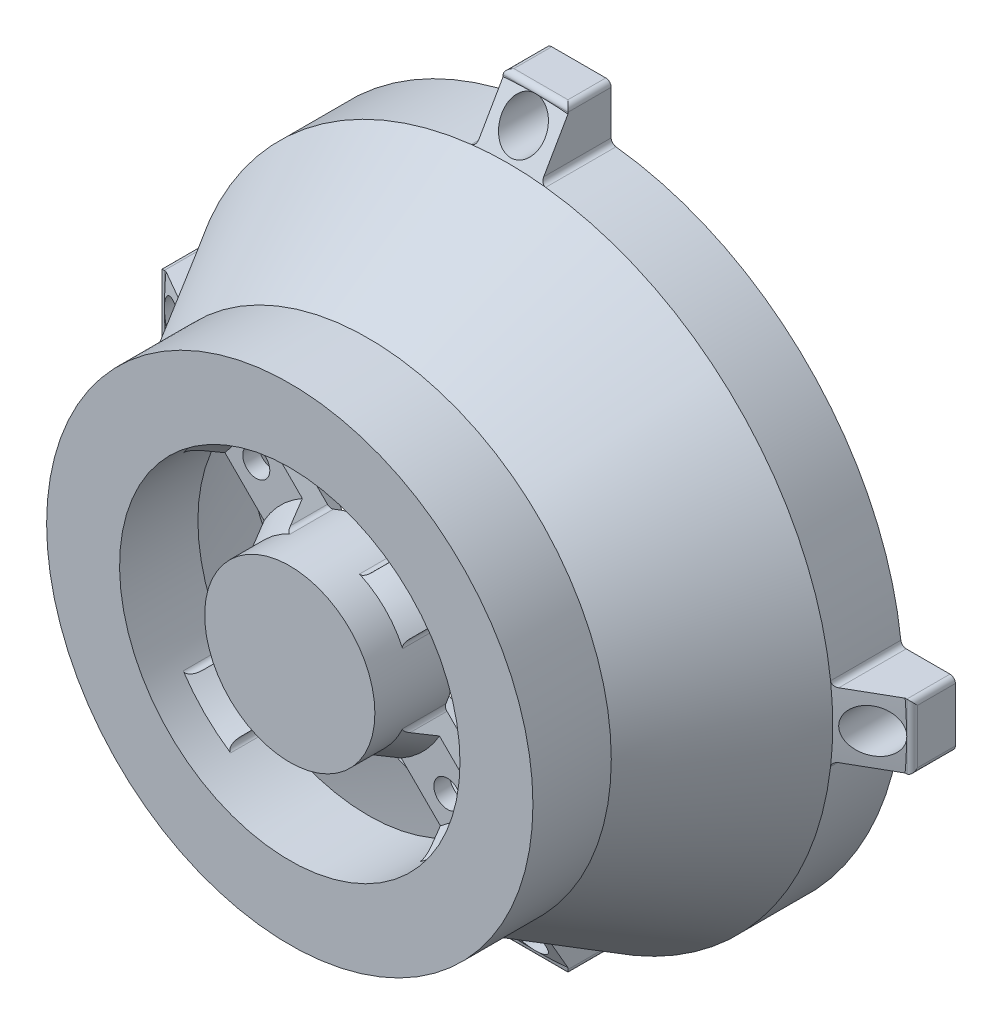
SolidWorks part; units mm, degrees
note: The reader was unsure of these and kept them because the rebuilt part matched: shared geometry of "Sketch1<3>".
ref_plane "Front Plane" through (0, 0, 0) normal (0, 0, 1) x (1, 0, 0)
ref_plane "Top Plane" through (0, 0, 0) normal (0, 1, 0) x (1, 0, 0)
ref_plane "Right Plane" through (0, 0, 0) normal (1, 0, 0) x (0, 0, -1)
sketch "Sketch1" plane through (0, 0, 0) normal (0, 0, 1) x (1, 0, 0)
  line L0 (0, 45) -> (0, 0) construction
  line L1 (17.6777, 17.6777) -> (0, 0) construction
  circle A0 centre (0, 0) radius 45
  circle A1 centre (0, 0) radius 25 construction
  circle A2 centre (17.6777, 17.6777) radius 2.5
  circle A3 centre (17.6777, -17.6777) radius 2.5
  circle A4 centre (-17.6777, -17.6777) radius 2.5
  circle A5 centre (-17.6777, 17.6777) radius 2.5
  circle A6 centre (0, 0) radius 15.75
  circle A7 centre (0, 0) radius 31.5
  point P16 (0, 0)
  point P27 (-1.0882, 1.0882)
  point P29 (2.5, -2.5)
  point P30 (0, 0)
  dimension "D2" = 50
  dimension "D4" = 5
  dimension "D6" = 31.5
  dimension "D7" = 63
  dimension "D8" = 90
  dimension "D3" = 45
  dimension "D5" = 4
extrude "Boss-Extrude1" add sketch "Sketch1" along normal blind 14.5 contours A6 | A0 A7
extrude "Boss-Extrude2" add sketch "Sketch1<3>" along normal blind 8 contours A7 A2 A3 A4 A5 A6
sketch "Sketch1<3>" plane through (0, 0, 0) normal (0, 0, 1) x (1, 0, 0) same geometry as "Sketch1"
sketch "Sketch6" plane through (0, 0, 8) normal (0, 0, 1) x (1, 0, 0)
  line L0 (-17.6777, 17.6777) -> (-22.2739, 22.2739) construction
  line L1 (-18.4559, 25.527) -> (-7.0253, 14.0964)
  line L2 (-21.2132, 14.1421) -> (-14.1421, 21.2132) construction
  line L3 (-14.0964, 7.0253) -> (-25.527, 18.4559)
  line L4 (25.527, 18.4559) -> (14.0964, 7.0253)
  line L5 (7.0253, 14.0964) -> (18.4559, 25.527)
  line L6 (18.4559, -25.527) -> (7.0253, -14.0964)
  line L7 (14.0964, -7.0253) -> (25.527, -18.4559)
  line L8 (-25.527, -18.4559) -> (-14.0964, -7.0253)
  line L9 (-7.0253, -14.0964) -> (-18.4559, -25.527)
  arc A0 (-25.527, 18.4559) -> (-25.527, -18.4559) centre (0, 0) ccw
  circle A1 centre (0, 0) radius 31.5 construction
  circle A2 centre (0, 0) radius 15.75 construction
  arc A3 (-14.0964, 7.0253) -> (-14.0964, -7.0253) centre (0, 0) ccw
  arc A4 (7.0253, 14.0964) -> (-7.0253, 14.0964) centre (0, 0) ccw
  arc A5 (14.0964, -7.0253) -> (14.0964, 7.0253) centre (0, 0) ccw
  arc A6 (-7.0253, -14.0964) -> (7.0253, -14.0964) centre (0, 0) ccw
  arc A7 (18.4559, 25.527) -> (-18.4559, 25.527) centre (0, 0) ccw
  arc A8 (25.527, -18.4559) -> (25.527, 18.4559) centre (0, 0) ccw
  arc A9 (-18.4559, -25.527) -> (18.4559, -25.527) centre (0, 0) ccw
  point P16 (-17.6777, 17.6777)
  point P33 (0, 0)
  dimension "D1" = 10
extrude "Cut-Extrude1" cut sketch "Sketch6" against normal up to surface (8 mm away) up to face at (20.1777, 17.6777, 0)
sketch "Sketch2" plane through (0, 0, 0) normal (0, 1, 0) x (1, 0, 0)
  line L0 (-45, 0) -> (-60, 25.9808)
  line L1 (-60, 25.9808) -> (-60, 30.9808)
  line L2 (-60, 30.9808) -> (-50, 30.9808)
  line L3 (-50, 30.9808) -> (-50, 25.9808)
  line L4 (-50, 25.9808) -> (-35, 0)
  line L5 (45, 0) -> (-45, 0) construction
  line L6 (-35, 0) -> (-45, 0)
  line L7 (0, 0) -> (0, -50000) construction
  point P12 (0, 0)
  dimension "D1" = 10
  dimension "D2" = 5
  dimension "D3" = 60
  dimension "D4" = 60
revolve "Revolve1" add sketch "Sketch2" angle 360 about L7
sketch "Sketch4" plane through (0, 0, -30.9808) normal (0, 0, -1) x (-1, 0, 0)
  line L0 (0, 69.6992) -> (0, 0) construction
  line L1 (-6, 69.6992) -> (6, 69.6992)
  line L2 (-6, 69.6992) -> (-6, 59.6992)
  line L4 (6, 69.6992) -> (6, 59.6992)
  line L5 (-6, 69.6992) -> (0, 60) construction
  line L6 (0, 60) -> (6, 69.6992) construction
  line L8 (69.6992, 6) -> (69.6992, -6)
  line L9 (69.6992, -6) -> (59.6992, -6)
  line L10 (69.6992, 6) -> (59.6992, 6)
  line L11 (6, -69.6992) -> (-6, -69.6992)
  line L12 (-6, -69.6992) -> (-6, -59.6992)
  line L13 (6, -69.6992) -> (6, -59.6992)
  line L14 (-69.6992, -6) -> (-69.6992, 6)
  line L15 (-69.6992, 6) -> (-59.6992, 6)
  line L16 (-69.6992, -6) -> (-59.6992, -6)
  arc A0 (-6, 59.6992) -> (-59.6992, 6) centre (0, 0) ccw
  circle A1 centre (0, 0) radius 60 construction
  circle A2 centre (0, 64.6992) radius 4
  circle A3 centre (64.6992, 0) radius 4
  circle A4 centre (0, -64.6992) radius 4
  circle A5 centre (-64.6992, 0) radius 4
  arc A6 (59.6992, 6) -> (6, 59.6992) centre (0, 0) ccw
  arc A7 (6, -59.6992) -> (59.6992, -6) centre (0, 0) ccw
  arc A8 (-59.6992, -6) -> (-6, -59.6992) centre (0, 0) ccw
  circle A9 centre (0, 0) radius 50
  circle A10 centre (0, 0) radius 50 construction
  point P5 (0, 60)
  point P36 (0, 0)
  dimension "D2" = 5
  dimension "D1" = 8
  dimension "D3" = 10
  dimension "D5" = 12
  dimension "D4" = 4
extrude "Boss-Extrude3" add sketch "Sketch4" along normal blind 8
sketch "Sketch5" plane through (0, 0, 0) normal (0, 1, 0) x (1, 0, 0)
  line L0 (0, 0) -> (0, -50000) construction
  line L2 (-15.75, -8) -> (15.75, -8) construction
  line L3 (-15.75, -8) -> (-18.625, -3.0204)
  line L4 (-18.625, -3.0204) -> (-28.625, -3.0204)
  line L5 (-28.625, -3.0204) -> (-31.5, -8)
  line L6 (-31.5, -8) -> (-15.75, -8)
  dimension "D1" = 15.75
  dimension "D2" = 31.5
  dimension "D3" = 60
  dimension "D4" = 60
  dimension "D5" = 10
revolve "Cut-Revolve1" cut sketch "Sketch5" angle 360 about L0
chamfer "Chamfer1" distance 5 angle 60 4 edges at (0, 60, -30.9808) (0, -60, -30.9808) (-60, 0, -30.9808) (60, 0, -30.9808)
fillet "Fillet1" radius 1 36 edges at (-59.6992, 6, -32.4808) (-69.6992, 6, -34.9808) (-69.6992, -6, -34.9808) (-59.6992, -6, -32.4808) (-6, -69.6992, -34.9808) (-6, -59.6992, -32.4808) (6, -59.6992, -32.4808) (6, -69.6992, -34.9808) (59.6992, -6, -32.4808) (59.6992, 6, -32.4808) (69.6992, -6, -34.9808) (69.6992, 6, -34.9808) (6, 59.6992, -32.4808) (-6, 59.6992, -32.4808) (-6, 69.6992, -34.9808) (6, 69.6992, -34.9808) (-18.4559, 25.527, 4) (-25.527, 18.4559, 4) (-18.4559, -25.527, 4) (-25.527, -18.4559, 4) (18.4559, -25.527, 4) (14.0964, -7.0253, 4) (25.527, -18.4559, 4) (25.527, 18.4559, 4) (14.0964, 7.0253, 4) (7.0253, 14.0964, 4) (-7.0253, 14.0964, 4) (18.4559, 25.527, 4) (-14.0964, 7.0253, 4) (-14.0964, -7.0253, 4) (-7.0253, -14.0964, 4) (7.0253, -14.0964, 4) (-69.6992, 0, -30.9808) (0, -69.6992, -30.9808) (69.6992, 0, -30.9808) (0, 69.6992, -30.9808)
equation "\"M6 Screw\"= 5mm"
equation "\"Flange to Part A\"= 90mm"
equation "\"Part A to Part b\"= 120mm"
equation "\"Part B to Part C\"= 120"
equation "\"D4@Sketch1\"=\"M6 Screw\""
equation "\"D8@Sketch1\"=\"Flange to Part A\""
equation "\"D4@Sketch2\"=\"Part A to Part b\"/2"
equation "\"Part B Screw to Wall\"= 5mm"
equation "\"Heat Set Insert Diameter\"= 8mm"
equation "\"D1@Sketch4\"=\"Heat Set Insert Diameter\""
equation "\"D1@Sketch3\" = \"Part B Screw to Wall\""
